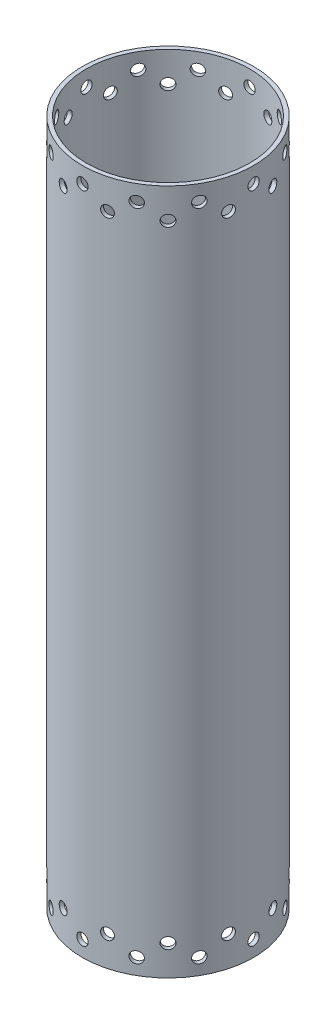
SolidWorks part; units mm, degrees
material "6061-T6 (SS)"
ref_plane "Front Plane" through (0, 0, 0) normal (0, 0, 1) x (1, 0, 0)
ref_plane "Top Plane" through (0, 0, 0) normal (0, 1, 0) x (1, 0, 0)
ref_plane "Right Plane" through (0, 0, 0) normal (1, 0, 0) x (0, 0, -1)
sketch "Sketch2" plane through (0, 0, 0) normal (0, 1, 0) x (1, 0, 0)
  circle A0 centre (0, 0) radius 76.2
  circle A1 centre (0, 0) radius 72.5932
  dimension "D1" = 152.4
  dimension "D2" = 145.1864
extrude "Boss-Extrude1" add sketch "Sketch2" along normal blind 609.6
sketch "Sketch3" plane through (0, 0, 0) normal (0, 0, 1) x (1, 0, 0)
  line L0 (0, 609.6) -> (0, 595.503) construction
  line L1 (72.5932, 609.6) -> (-72.5932, 609.6) construction
  circle A0 centre (0, 595.503) radius 5.0419
  dimension "D1" = 10.0838
  dimension "D2" = 14.097
extrude "Cut-Extrude1" cut sketch "Sketch3" against normal blind 1143
ref_plane "Plane1" through (-19.722, 0, 73.6035) normal (-0.2588, 0, 0.9659) x (0, -1, 0)
sketch "Sketch6" plane through (-19.722, 0, 73.6035) normal (-0.2588, 0, 0.9659) x (0, -1, 0)
  line L0 (-609.6, 0) -> (-582.803, 0) construction
  line L1 (-609.6, 76.2) -> (-609.6, -76.2) construction
  circle A0 centre (-582.803, 0) radius 5.0419
  dimension "D1" = 10.0838
  dimension "D2" = 26.797
extrude "Cut-Extrude2" cut sketch "Sketch6" against normal blind 25.4
pattern_circular "CirPattern2" count 12 over 360 about axis through (0, 609.6, 0) along (0, -1, 0) of "Cut-Extrude2", "Cut-Extrude1"
ref_plane "Plane2" through (0, 304.8, 0) normal (0, 1, 0) x (1, 0, 0)
mirror "Mirror1" about plane through (0, 304.8, 0) normal (0, 1, 0) of "CirPattern2"
equation "\"holeDia\"=0.397"
equation "\"D1@Sketch3\"=\"holeDia\""
equation "\"D1@Sketch6\"=\"holeDia\""
equation "\"numHoles\"=12"
equation "\"D1@CirPattern2\"=\"numHoles\""
equation "\"D1@Plane1\"=180/\"numHoles\""
equation "\"D2@Sketch6\"=\"D2@Sketch3\"+.5"
